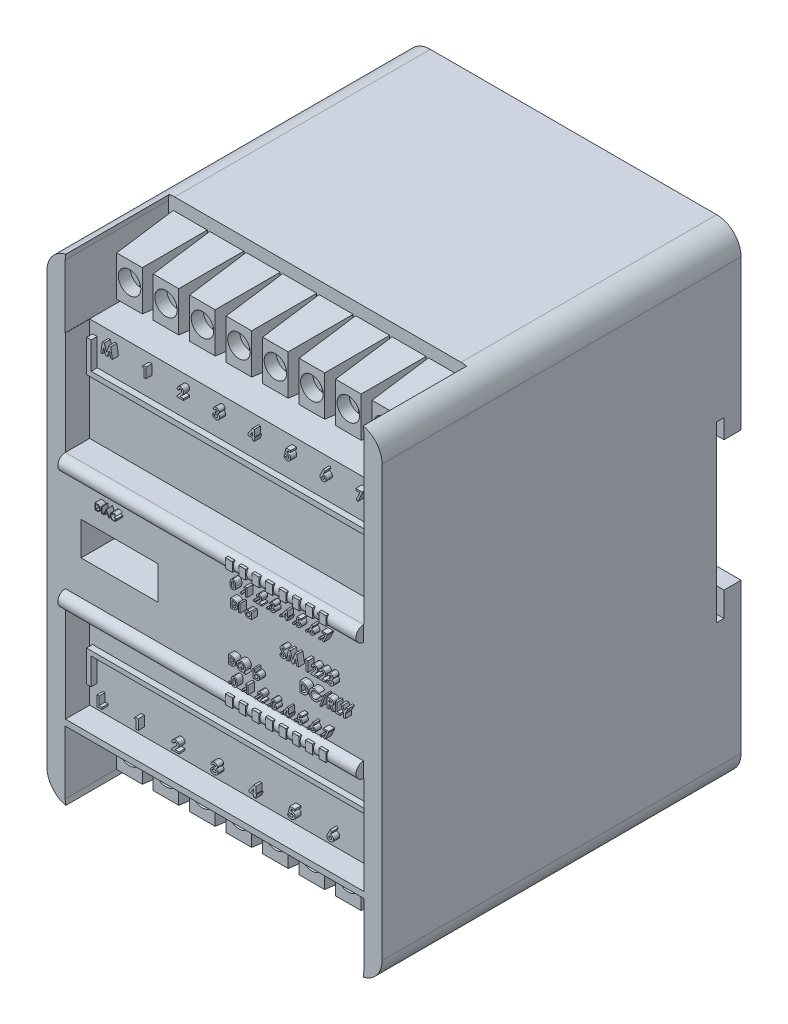
SolidWorks part; units mm, degrees
ref_plane "Alzado" through (0, 0, 0) normal (0, 0, 1) x (1, 0, 0)
ref_plane "Planta" through (0, 0, 0) normal (0, 1, 0) x (1, 0, 0)
ref_plane "Vista lateral" through (0, 0, 0) normal (1, 0, 0) x (0, 0, -1)
sketch "Croquis1" plane through (0, 0, 0) normal (0, 0, 1) x (1, 0, 0)
  line L1 (-29.92, 50) -> (29.92, 50)
  line L2 (-35, 44.92) -> (-35, -44.92)
  line L3 (-29.92, -50) -> (29.92, -50)
  line L4 (35, 44.92) -> (35, -44.92)
  line L5 (-35, 50) -> (35, -50) construction
  line L6 (-35, -50) -> (35, 50) construction
  arc A0 (-35, 44.92) -> (-29.92, 50) centre (-29.92, 44.92) cw
  arc A1 (29.92, 50) -> (35, 44.92) centre (29.92, 44.92) cw
  arc A2 (35, -44.92) -> (29.92, -50) centre (29.92, -44.92) cw
  arc A3 (-29.92, -50) -> (-35, -44.92) centre (-29.92, -44.92) cw
  point P0 (0, 0)
  dimension "D3" = 5.08
  dimension "D1" = 70
  dimension "D2" = 100
extrude "Saliente-Extruir1" add sketch "Croquis1" along normal blind 75
sketch "Croquis2" plane through (0, 0, 75) normal (0, 0, 1) x (1, 0, 0)
  line L0 (35, -44.92) -> (35, 44.92) construction
  line L1 (-31.19, 35.56) -> (31.19, 35.56)
  line L2 (-48.7595, 0) -> (42.216, 0) construction
  line L3 (31.19, -35.56) -> (31.19, -48.73)
  line L4 (-27.8625, -3.4828) -> (-11.8205, -3.4828)
  line L5 (-27.8625, -3.4828) -> (-27.8625, 3.4828)
  line L6 (-27.8625, 3.4828) -> (-11.8205, 3.4828)
  line L7 (-35, 44.92) -> (-35, -44.92) construction
  line L8 (-31.19, 35.56) -> (31.19, 35.56)
  line L9 (-31.19, 35.56) -> (-31.19, 48.73)
  line L10 (-26.11, 53.81) -> (26.11, 53.81)
  line L11 (31.19, 35.56) -> (31.19, 48.73)
  line L12 (29.92, 50) -> (-29.92, 50) construction
  line L13 (-11.8205, -3.4828) -> (-11.8205, 3.4828)
  line L14 (-26.11, -53.81) -> (26.11, -53.81)
  line L15 (-31.19, -35.56) -> (-31.19, -48.73)
  line L16 (-31.19, -35.56) -> (31.19, -35.56)
  line L17 (-27.8625, -3.4828) -> (-11.8205, 3.4828) construction
  line L18 (-27.8625, 3.4828) -> (-11.8205, -3.4828) construction
  arc A0 (31.19, 48.73) -> (26.11, 53.81) centre (26.11, 48.73) ccw
  arc A1 (-26.11, 53.81) -> (-31.19, 48.73) centre (-26.11, 48.73) ccw
  arc A2 (31.19, -48.73) -> (26.11, -53.81) centre (26.11, -48.73) cw
  arc A3 (-26.11, -53.81) -> (-31.19, -48.73) centre (-26.11, -48.73) cw
  point P0 (0, 0)
  point P1 (-19.8415, 0)
  dimension "D5" = 5.08
  dimension "D1" = 35.56
  dimension "D2" = 3.81
  dimension "D3" = 3.81
  dimension "D4" = 3.81
extrude "Cortar-Extruir1" cut sketch "Croquis2" against normal blind 21.59 contours L10 A1 L9 L1 L11 A0 | L4 L13 L6 L5 | L3 A3 region at (0, 44.6065, 75) region at (0, -44.6065, 75) region at (-19.8415, 0, 75)
sketch "Croquis3" plane through (0, 0, 0) normal (1, 0, 0) x (0, 0, -1)
  line L0 (-75, -44.92) -> (-75, 44.92) construction
  circle A0 centre (-75, 12.3674) radius 1.5875
  circle A1 centre (-75, -12.2706) radius 1.5875
  dimension "D1" = 3.175
  dimension "D2" = 2
extrude "Saliente-Extruir2" add sketch "Croquis3" along normal mid plane 62.3
sketch "Croquis5" plane through (0, 0, 75) normal (0, 0, 1) x (1, 0, 0)
  line L0 (31.19, 35.56) -> (31.19, 48.73) construction
  line L1 (-31.15, 13.9549) -> (31.19, 13.9549)
  line L2 (-31.15, 13.9549) -> (-31.15, 36.8334)
  line L3 (-31.15, 36.8334) -> (31.19, 36.8334)
  line L4 (31.19, 13.9549) -> (31.19, 36.8334)
  line L5 (31.19, -35.56) -> (31.19, -48.73) construction
  line L6 (-31.15, -13.8581) -> (31.19, -13.8581)
  line L7 (-31.15, -13.8581) -> (-31.15, -34.3005)
  line L8 (-31.15, -34.3005) -> (31.19, -34.3005)
  line L9 (31.19, -13.8581) -> (31.19, -34.3005)
extrude "Cortar-Extruir2" cut sketch "Croquis5" against normal blind 5.08
sketch "Croquis6" plane through (0, 0, 53.41) normal (0, 0, 1) x (1, 0, 0)
  line L0 (-22.5856, 47.4156) -> (-15.4736, 47.4156)
  line L1 (-30.2056, 47.4156) -> (-23.0936, 47.4156)
  line L2 (-30.2056, 47.4156) -> (-30.2056, 37.2556)
  line L3 (-30.2056, 37.2556) -> (-23.0936, 37.2556)
  line L4 (-23.0936, 47.4156) -> (-23.0936, 37.2556)
  line L5 (-22.5856, 47.4156) -> (-22.5856, 37.2556)
  line L6 (-22.5856, 37.2556) -> (-15.4736, 37.2556)
  line L7 (-15.4736, 47.4156) -> (-15.4736, 37.2556)
  line L8 (-14.9656, 47.4156) -> (-7.8536, 47.4156)
  line L9 (-14.9656, 47.4156) -> (-14.9656, 37.2556)
  line L10 (-14.9656, 37.2556) -> (-7.8536, 37.2556)
  line L11 (-7.8536, 47.4156) -> (-7.8536, 37.2556)
  line L12 (-7.3456, 47.4156) -> (-0.2336, 47.4156)
  line L13 (-7.3456, 47.4156) -> (-7.3456, 37.2556)
  line L14 (-7.3456, 37.2556) -> (-0.2336, 37.2556)
  line L15 (-0.2336, 47.4156) -> (-0.2336, 37.2556)
  line L16 (0.2744, 47.4156) -> (7.3864, 47.4156)
  line L17 (0.2744, 47.4156) -> (0.2744, 37.2556)
  line L18 (0.2744, 37.2556) -> (7.3864, 37.2556)
  line L19 (7.3864, 47.4156) -> (7.3864, 37.2556)
  line L20 (7.8944, 47.4156) -> (15.0064, 47.4156)
  line L21 (7.8944, 47.4156) -> (7.8944, 37.2556)
  line L22 (7.8944, 37.2556) -> (15.0064, 37.2556)
  line L23 (15.0064, 47.4156) -> (15.0064, 37.2556)
  line L24 (15.5144, 47.4156) -> (22.6264, 47.4156)
  line L25 (15.5144, 47.4156) -> (15.5144, 37.2556)
  line L26 (15.5144, 37.2556) -> (22.6264, 37.2556)
  line L27 (22.6264, 47.4156) -> (22.6264, 37.2556)
  line L28 (23.1344, 47.4156) -> (30.2464, 47.4156)
  line L29 (23.1344, 47.4156) -> (23.1344, 37.2556)
  line L30 (23.1344, 37.2556) -> (30.2464, 37.2556)
  line L31 (30.2464, 47.4156) -> (30.2464, 37.2556)
  line L32 (-22.5856, -37.6744) -> (-15.4736, -37.6744)
  line L33 (-22.5856, -37.6744) -> (-22.5856, -47.8344)
  line L34 (-22.5856, -47.8344) -> (-15.4736, -47.8344)
  line L35 (-15.4736, -37.6744) -> (-15.4736, -47.8344)
  line L36 (-14.9656, -37.6744) -> (-7.8536, -37.6744)
  line L37 (-14.9656, -37.6744) -> (-14.9656, -47.8344)
  line L38 (-14.9656, -47.8344) -> (-7.8536, -47.8344)
  line L39 (-7.8536, -37.6744) -> (-7.8536, -47.8344)
  line L40 (-7.3456, -37.6744) -> (-0.2336, -37.6744)
  line L41 (-7.3456, -37.6744) -> (-7.3456, -47.8344)
  line L42 (-7.3456, -47.8344) -> (-0.2336, -47.8344)
  line L43 (-0.2336, -37.6744) -> (-0.2336, -47.8344)
  line L44 (0.2744, -37.6744) -> (7.3864, -37.6744)
  line L45 (0.2744, -37.6744) -> (0.2744, -47.8344)
  line L46 (0.2744, -47.8344) -> (7.3864, -47.8344)
  line L47 (7.3864, -37.6744) -> (7.3864, -47.8344)
  line L48 (7.8944, -37.6744) -> (15.0064, -37.6744)
  line L49 (7.8944, -37.6744) -> (7.8944, -47.8344)
  line L50 (7.8944, -47.8344) -> (15.0064, -47.8344)
  line L51 (15.0064, -37.6744) -> (15.0064, -47.8344)
  line L52 (15.5144, -37.6744) -> (22.6264, -37.6744)
  line L53 (15.5144, -37.6744) -> (15.5144, -47.8344)
  line L54 (15.5144, -47.8344) -> (22.6264, -47.8344)
  line L55 (22.6264, -37.6744) -> (22.6264, -47.8344)
  line L56 (23.1344, -37.6744) -> (30.2464, -37.6744)
  line L57 (23.1344, -37.6744) -> (23.1344, -47.8344)
  line L58 (23.1344, -47.8344) -> (30.2464, -47.8344)
  line L59 (30.2464, -37.6744) -> (30.2464, -47.8344)
  line L60 (-30.2056, -37.6744) -> (-23.0936, -37.6744)
  line L61 (-30.2056, -37.6744) -> (-30.2056, -47.8344)
  line L62 (-30.2056, -47.8344) -> (-23.0936, -47.8344)
  line L63 (-23.0936, -37.6744) -> (-23.0936, -47.8344)
  dimension "D1" = 7.112
  dimension "D2" = 10.16
extrude "Saliente-Extruir4" add sketch "Croquis6" along normal blind 12.7 draft 4
sketch "Croquis7" plane through (0, 0, 66.11) normal (0, 0, 1) x (1, 0, 0)
  circle A0 centre (-26.64, 42.5137) radius 2.3546
  circle A1 centre (-19.02, 42.5137) radius 2.3546
  circle A2 centre (-11.4, 42.5137) radius 2.3546
  circle A3 centre (-3.78, 42.5137) radius 2.3546
  circle A4 centre (3.84, 42.5137) radius 2.3546
  circle A5 centre (11.46, 42.5137) radius 2.3546
  circle A6 centre (19.08, 42.5137) radius 2.3546
  circle A7 centre (26.7, 42.5137) radius 2.3546
  circle A8 centre (-19.02, -42.5763) radius 2.3546
  circle A9 centre (-11.4, -42.5763) radius 2.3546
  circle A10 centre (-3.78, -42.5763) radius 2.3546
  circle A11 centre (3.84, -42.5763) radius 2.3546
  circle A12 centre (11.46, -42.5763) radius 2.3546
  circle A13 centre (19.08, -42.5763) radius 2.3546
  circle A14 centre (26.7, -42.5763) radius 2.3546
  circle A15 centre (-26.64, -42.5763) radius 2.3546
  point P2 (-26.64, 42.5137)
  dimension "D1" = 8
  dimension "D2" = 2
extrude "Cortar-Extruir3" cut sketch "Croquis7" against normal blind 2.54
sketch "Croquis8" plane through (0, 0, 63.57) normal (0, 0, 1) x (1, 0, 0)
  line L0 (-18.6399, 44.8375) -> (-18.6399, 40.1899)
  line L1 (-27.02, 44.8375) -> (-26.2599, 44.8375)
  line L2 (-27.02, 44.8375) -> (-27.02, 40.1899)
  line L3 (-27.02, 40.1899) -> (-26.2599, 40.1899)
  line L4 (-26.2599, 44.8375) -> (-26.2599, 40.1899)
  line L5 (-27.02, 44.8375) -> (-26.2599, 40.1899) construction
  line L6 (-27.02, 40.1899) -> (-26.2599, 44.8375) construction
  line L7 (-19.4, 44.8375) -> (-19.4, 40.1899)
  line L8 (-19.4, 44.8375) -> (-18.6399, 44.8375)
  line L9 (-19.4, 40.1899) -> (-18.6399, 40.1899)
  line L10 (-11.0199, 44.8375) -> (-11.0199, 40.1899)
  line L11 (-11.78, 44.8375) -> (-11.78, 40.1899)
  line L12 (-11.78, 44.8375) -> (-11.0199, 44.8375)
  line L13 (-11.78, 40.1899) -> (-11.0199, 40.1899)
  line L14 (-3.3999, 44.8375) -> (-3.3999, 40.1899)
  line L15 (-4.16, 44.8375) -> (-4.16, 40.1899)
  line L16 (-4.16, 44.8375) -> (-3.3999, 44.8375)
  line L17 (-4.16, 40.1899) -> (-3.3999, 40.1899)
  line L18 (4.2201, 44.8375) -> (4.2201, 40.1899)
  line L19 (3.46, 44.8375) -> (3.46, 40.1899)
  line L20 (3.46, 44.8375) -> (4.2201, 44.8375)
  line L21 (3.46, 40.1899) -> (4.2201, 40.1899)
  line L22 (11.8401, 44.8375) -> (11.8401, 40.1899)
  line L23 (11.08, 44.8375) -> (11.08, 40.1899)
  line L24 (11.08, 44.8375) -> (11.8401, 44.8375)
  line L25 (11.08, 40.1899) -> (11.8401, 40.1899)
  line L26 (19.4601, 44.8375) -> (19.4601, 40.1899)
  line L27 (18.7, 44.8375) -> (18.7, 40.1899)
  line L28 (18.7, 44.8375) -> (19.4601, 44.8375)
  line L29 (18.7, 40.1899) -> (19.4601, 40.1899)
  line L30 (27.0801, 44.8375) -> (27.0801, 40.1899)
  line L31 (26.32, 44.8375) -> (26.32, 40.1899)
  line L32 (26.32, 44.8375) -> (27.0801, 44.8375)
  line L33 (26.32, 40.1899) -> (27.0801, 40.1899)
  line L34 (-18.6399, -40.2525) -> (-18.6399, -44.9001)
  line L35 (-19.4, -40.2525) -> (-19.4, -44.9001)
  line L36 (-19.4, -40.2525) -> (-18.6399, -40.2525)
  line L37 (-19.4, -44.9001) -> (-18.6399, -44.9001)
  line L38 (-11.0199, -40.2525) -> (-11.0199, -44.9001)
  line L39 (-11.78, -40.2525) -> (-11.78, -44.9001)
  line L40 (-11.78, -40.2525) -> (-11.0199, -40.2525)
  line L41 (-11.78, -44.9001) -> (-11.0199, -44.9001)
  line L42 (-3.3999, -40.2525) -> (-3.3999, -44.9001)
  line L43 (-4.16, -40.2525) -> (-4.16, -44.9001)
  line L44 (-4.16, -40.2525) -> (-3.3999, -40.2525)
  line L45 (-4.16, -44.9001) -> (-3.3999, -44.9001)
  line L46 (4.2201, -40.2525) -> (4.2201, -44.9001)
  line L47 (3.46, -40.2525) -> (3.46, -44.9001)
  line L48 (3.46, -40.2525) -> (4.2201, -40.2525)
  line L49 (3.46, -44.9001) -> (4.2201, -44.9001)
  line L50 (11.8401, -40.2525) -> (11.8401, -44.9001)
  line L51 (11.08, -40.2525) -> (11.08, -44.9001)
  line L52 (11.08, -40.2525) -> (11.8401, -40.2525)
  line L53 (11.08, -44.9001) -> (11.8401, -44.9001)
  line L54 (19.4601, -40.2525) -> (19.4601, -44.9001)
  line L55 (18.7, -40.2525) -> (18.7, -44.9001)
  line L56 (18.7, -40.2525) -> (19.4601, -40.2525)
  line L57 (18.7, -44.9001) -> (19.4601, -44.9001)
  line L58 (27.0801, -40.2525) -> (27.0801, -44.9001)
  line L59 (26.32, -40.2525) -> (26.32, -44.9001)
  line L60 (26.32, -40.2525) -> (27.0801, -40.2525)
  line L61 (26.32, -44.9001) -> (27.0801, -44.9001)
  line L62 (-26.2599, -40.2525) -> (-26.2599, -44.9001)
  line L63 (-27.02, -40.2525) -> (-27.02, -44.9001)
  line L64 (-27.02, -40.2525) -> (-26.2599, -40.2525)
  line L65 (-27.02, -44.9001) -> (-26.2599, -44.9001)
  circle A0 centre (-26.64, 42.5137) radius 2.3546 construction
  point P0 (-26.64, 42.5137)
extrude "Cortar-Extruir4" cut sketch "Croquis8" against normal blind 1.27
sketch "Croquis9" plane through (0, 0, 75) normal (0, 0, 1) x (1, 0, 0)
  text T0 "<b>SM 1223</b>\r\n<b>     DC/RLY</b>" font "Century Gothic" height in points 8
  text T1 "<b>0 .1 .2 .3 .4 .5 .6 .7</b>\r\n<b>DI a</b>" font "Century Gothic" height 1.778
  text T2 "<b>DQ  b</b>\r\n<b>.0 .1 .2 .3 .4 .5 .6 .7</b>" font "Century Gothic" height 1.778
  text T3 "DIAG" font "Century Gothic" height in points 5
  point P4 (0, 0)
  point P5 (0, 0)
  point P6 (0, 0)
extrude "Saliente-Extruir5" add sketch "Croquis9" along normal blind 1.27
sketch "Croquis10" plane through (0, 0, 0) normal (0, 0, 1) x (1, 0, 0)
  line L0 (20.8081, 13.3932) -> (20.8081, 11.4451)
  line L1 (23.6021, 13.3932) -> (25.0607, 13.3932)
  line L2 (23.6021, 13.3932) -> (23.6021, 11.4451)
  line L3 (23.6021, 11.4451) -> (25.0607, 11.4451)
  line L4 (25.0607, 13.3932) -> (25.0607, 11.4451)
  line L5 (23.6021, 13.3932) -> (25.0607, 11.4451) construction
  line L6 (23.6021, 11.4451) -> (25.0607, 13.3932) construction
  line L7 (22.2667, 13.3932) -> (22.2667, 11.4451)
  line L8 (20.8081, 11.4451) -> (22.2667, 11.4451)
  line L9 (20.8081, 13.3932) -> (22.2667, 13.3932)
  line L10 (18.0141, 13.3932) -> (18.0141, 11.4451)
  line L11 (19.4727, 13.3932) -> (19.4727, 11.4451)
  line L12 (18.0141, 11.4451) -> (19.4727, 11.4451)
  line L13 (18.0141, 13.3932) -> (19.4727, 13.3932)
  line L14 (15.2201, 13.3932) -> (15.2201, 11.4451)
  line L15 (16.6787, 13.3932) -> (16.6787, 11.4451)
  line L16 (15.2201, 11.4451) -> (16.6787, 11.4451)
  line L17 (15.2201, 13.3932) -> (16.6787, 13.3932)
  line L18 (12.4261, 13.3932) -> (12.4261, 11.4451)
  line L19 (13.8847, 13.3932) -> (13.8847, 11.4451)
  line L20 (12.4261, 11.4451) -> (13.8847, 11.4451)
  line L21 (12.4261, 13.3932) -> (13.8847, 13.3932)
  line L22 (9.6321, 13.3932) -> (9.6321, 11.4451)
  line L23 (11.0907, 13.3932) -> (11.0907, 11.4451)
  line L24 (9.6321, 11.4451) -> (11.0907, 11.4451)
  line L25 (9.6321, 13.3932) -> (11.0907, 13.3932)
  line L26 (6.8381, 13.3932) -> (6.8381, 11.4451)
  line L27 (8.2967, 13.3932) -> (8.2967, 11.4451)
  line L28 (6.8381, 11.4451) -> (8.2967, 11.4451)
  line L29 (6.8381, 13.3932) -> (8.2967, 13.3932)
  line L30 (4.0441, 13.3932) -> (4.0441, 11.4451)
  line L31 (5.5027, 13.3932) -> (5.5027, 11.4451)
  line L32 (4.0441, 11.4451) -> (5.5027, 11.4451)
  line L33 (4.0441, 13.3932) -> (5.5027, 13.3932)
  line L34 (20.8081, -11.2448) -> (20.8081, -13.1929)
  line L35 (22.2667, -11.2448) -> (22.2667, -13.1929)
  line L36 (20.8081, -13.1929) -> (22.2667, -13.1929)
  line L37 (20.8081, -11.2448) -> (22.2667, -11.2448)
  line L38 (18.0141, -11.2448) -> (18.0141, -13.1929)
  line L39 (19.4727, -11.2448) -> (19.4727, -13.1929)
  line L40 (18.0141, -13.1929) -> (19.4727, -13.1929)
  line L41 (18.0141, -11.2448) -> (19.4727, -11.2448)
  line L42 (15.2201, -11.2448) -> (15.2201, -13.1929)
  line L43 (16.6787, -11.2448) -> (16.6787, -13.1929)
  line L44 (15.2201, -13.1929) -> (16.6787, -13.1929)
  line L45 (15.2201, -11.2448) -> (16.6787, -11.2448)
  line L46 (12.4261, -11.2448) -> (12.4261, -13.1929)
  line L47 (13.8847, -11.2448) -> (13.8847, -13.1929)
  line L48 (12.4261, -13.1929) -> (13.8847, -13.1929)
  line L49 (12.4261, -11.2448) -> (13.8847, -11.2448)
  line L50 (9.6321, -11.2448) -> (9.6321, -13.1929)
  line L51 (11.0907, -11.2448) -> (11.0907, -13.1929)
  line L52 (9.6321, -13.1929) -> (11.0907, -13.1929)
  line L53 (9.6321, -11.2448) -> (11.0907, -11.2448)
  line L54 (6.8381, -11.2448) -> (6.8381, -13.1929)
  line L55 (8.2967, -11.2448) -> (8.2967, -13.1929)
  line L56 (6.8381, -13.1929) -> (8.2967, -13.1929)
  line L57 (6.8381, -11.2448) -> (8.2967, -11.2448)
  line L58 (4.0441, -11.2448) -> (4.0441, -13.1929)
  line L59 (5.5027, -11.2448) -> (5.5027, -13.1929)
  line L60 (4.0441, -13.1929) -> (5.5027, -13.1929)
  line L61 (4.0441, -11.2448) -> (5.5027, -11.2448)
  line L62 (23.6021, -11.2448) -> (23.6021, -13.1929)
  line L63 (25.0607, -11.2448) -> (25.0607, -13.1929)
  line L64 (23.6021, -13.1929) -> (25.0607, -13.1929)
  line L65 (23.6021, -11.2448) -> (25.0607, -11.2448)
  point P0 (24.3314, 12.4191)
extrude "Saliente-Extruir6" add sketch "Croquis10" along normal blind 1.27 from offset 75.5
sketch "Croquis11" plane through (0, 0, 69.92) normal (0, 0, 1) x (1, 0, 0)
  line L0 (-30.5451, -29.5654) -> (-30.5451, -23.0356)
  line L1 (-30.5451, -23.0356) -> (30.5599, -23.0356)
  line L2 (30.5599, -23.0356) -> (30.5599, -29.5654)
  line L3 (30.5599, -29.5654) -> (29.5976, -29.5654)
  line L4 (29.5976, -29.5654) -> (29.5976, -23.9979)
  line L5 (29.5976, -23.9979) -> (-29.5828, -23.9979)
  line L6 (-29.5828, -23.9979) -> (-29.5828, -29.5654)
  line L7 (-29.5828, -29.5654) -> (-30.5451, -29.5654)
  line L8 (-30.5451, 33.1681) -> (-30.5451, 26.4334)
  line L9 (-30.5451, 26.4334) -> (30.5599, 26.4334)
  line L10 (30.5599, 26.4334) -> (30.5599, 33.1681)
  line L11 (30.5599, 33.1681) -> (29.5976, 33.1681)
  line L12 (29.5976, 33.1681) -> (29.5976, 27.5143)
  line L13 (29.5976, 27.5143) -> (-29.5828, 27.5143)
  line L14 (-29.5828, 27.5143) -> (-29.5828, 33.1681)
  line L15 (-29.5828, 33.1681) -> (-30.5451, 33.1681)
  text T0 "<b>M 1 2 3 4 5 6 7</b>\r\n" font "Century Gothic" height in points 8
  text T1 "<b>L 1 2 3 4 5 6 7</b>" font "Century Gothic" height in points 8
extrude "Saliente-Extruir7" add sketch "Croquis11" along normal blind 1.27
sketch "Croquis12" plane through (0, 0, 0) normal (1, 0, 0) x (0, 0, -1)
  line L0 (-53.41, 50) -> (0, 50) construction
  line L1 (-3.556, 17.6) -> (-5.08, 17.6)
  line L2 (-3.556, 17.6) -> (-3.556, 13.589)
  line L3 (-3.556, -18.722) -> (-5.08, -18.722)
  line L4 (-5.08, 17.6) -> (-5.08, -18.722)
  line L5 (-3.556, -13.589) -> (-3.556, -18.722)
  line L6 (-3.556, -13.589) -> (2.54, -13.589)
  line L8 (-3.556, 13.589) -> (2.54, 13.589)
  line L9 (2.54, -13.589) -> (2.54, 13.589)
  line L10 (0, -44.92) -> (0, 44.92) construction
  dimension "D1" = 32.4
  dimension "D2" = 36.322
  dimension "D3" = 1.524
  dimension "D4" = 27.178
  dimension "D5" = 13.589
  dimension "D6" = 7.62
  dimension "D7" = 5.08
  dimension "D8" = 5.133
extrude "Cortar-Extruir5" cut sketch "Croquis12" against normal through all both and the other way through all
equation "\"75MMpulgadas\"=0"
